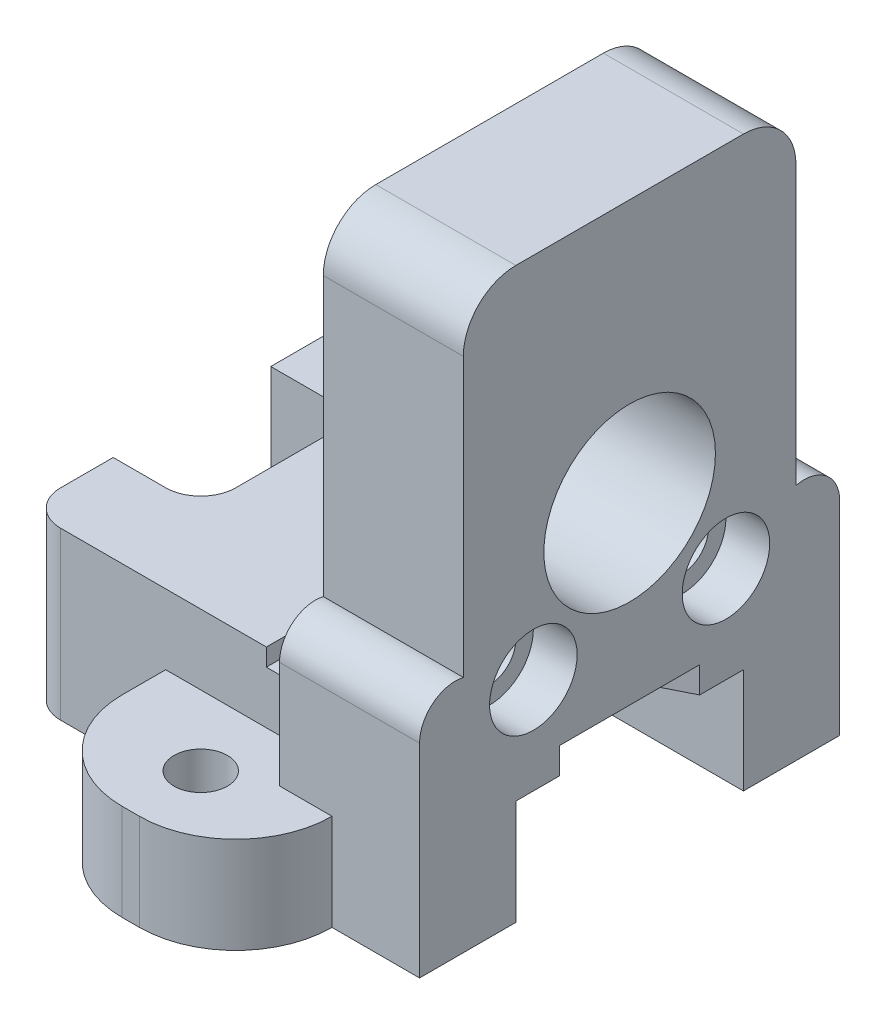
SolidWorks part; units mm, degrees
ref_plane "Front Plane" through (0, 0, 0) normal (0, 0, 1) x (1, 0, 0)
ref_plane "Top Plane" through (0, 0, 0) normal (0, 1, 0) x (1, 0, 0)
ref_plane "Right Plane" through (0, 0, 0) normal (1, 0, 0) x (0, 0, -1)
sketch "Sketch1" plane through (0, 0, 0) normal (0, 1, 0) x (1, 0, 0)
  line L0 (-1, -3) -> (23, -3)
  line L1 (0, 0) -> (22, 0)
  line L2 (0, 0) -> (0, 13)
  line L3 (0, 13) -> (22, 13)
  line L4 (22, 0) -> (22, 13)
  line L5 (25, -1) -> (25, 14)
  line L6 (-1, 16) -> (23, 16)
  line L7 (-3, -1) -> (-3, 14)
  line L8 (-3, -3) -> (25, -3) construction
  line L9 (25, -3) -> (25, 16) construction
  line L10 (-3, 16) -> (25, 16) construction
  line L11 (-3, -3) -> (-3, 16) construction
  line L12 (23, -3) -> (25, -3)
  line L13 (25, -3) -> (25, -1)
  line L14 (25, 16) -> (23, 16)
  line L15 (25, 16) -> (25, 14)
  arc A2 (-1, 16) -> (-3, 14) centre (-1, 14) ccw
  arc A3 (-1, -3) -> (-3, -1) centre (-1, -1) cw
  dimension "D1" = 22
  dimension "D2" = 13
  dimension "D3" = 3
extrude "Boss-Extrude1" add sketch "Sketch1" along normal blind 6
sketch "Sketch2" plane through (0, 6, 0) normal (0, 1, 0) x (1, 0, 0)
  line L0 (25, 14) -> (25, -1)
  line L1 (23, -3) -> (-1, -3)
  line L2 (-3, -1) -> (-3, 14)
  line L3 (-1, 16) -> (23, 16)
  line L4 (25, 16) -> (-1, 16) construction
  line L5 (23, -3) -> (25, -3)
  line L6 (25, -3) -> (25, -1)
  line L7 (25, 14) -> (25, 16)
  line L8 (25, 16) -> (23, 16)
  arc A1 (-1, -3) -> (-3, -1) centre (-1, -1) cw
  arc A2 (-3, 14) -> (-1, 16) centre (-1, 14) cw
extrude "Boss-Extrude2" add sketch "Sketch2" along normal blind 3.5
sketch "Sketch3" plane through (0, 0, 0) normal (0, -1, 0) x (1, 0, 0)
  line L0 (-1, 3) -> (25, 3) construction
  line L1 (5, 3) -> (17, 3)
  line L2 (5, 3) -> (5, 5.5)
  line L3 (10.5, 11) -> (11.5, 11)
  line L4 (17, 3) -> (17, 5.5)
  line L5 (25, -16) -> (-1, -16) construction
  line L6 (17, -16) -> (5, -16)
  line L7 (17, -16) -> (17, -18.5)
  line L8 (11.5, -24) -> (10.5, -24)
  line L9 (5, -16) -> (5, -18.5)
  line L10 (25, 3) -> (25, -16) construction
  line L11 (-3, -14) -> (-3, 1) construction
  arc A0 (17, -18.5) -> (11.5, -24) centre (11.5, -18.5) cw
  arc A1 (10.5, -24) -> (5, -18.5) centre (10.5, -18.5) cw
  arc A2 (5, 5.5) -> (10.5, 11) centre (10.5, 5.5) cw
  arc A3 (11.5, 11) -> (17, 5.5) centre (11.5, 5.5) cw
  point P16 (17, -17.25)
  point P19 (17, -24)
  point P26 (17, 11)
  dimension "D7" = 5.5
  dimension "D1" = 8
  dimension "D2" = 8
  dimension "D3" = 8
  dimension "D4" = 8
  dimension "D5" = 8
  dimension "D6" = 8
extrude "Boss-Extrude3" add sketch "Sketch3" against normal up to surface (9.5 mm away) up to face at (6.8619, 9.5, -6.5)
sketch "Sketch4" plane through (0, 0, 0) normal (0, -1, 0) x (-1, 0, 0)
  line L0 (-17, 18.5) -> (-17, 16) construction
  line L2 (-10.5, 24) -> (-11.5, 24) construction
  line L3 (-11.5, -11) -> (-10.5, -11) construction
  line L4 (-5, -5.5) -> (-5, -3) construction
  circle A0 centre (-11, 20) radius 1.525
  circle A1 centre (-11, -7) radius 1.524
  point P9 (-11, 24)
  dimension "D1" = 3.048
  dimension "D2" = 3.05
  dimension "D3" = 6
  dimension "D4" = 4
  dimension "D5" = 4
  dimension "D6" = 6
extrude "Cut-Extrude1" cut sketch "Sketch4" against normal through all
sketch "Sketch5" plane through (25, 0, 0) normal (1, 0, 0) x (0, 0, -1)
  line L0 (-3, 0) -> (16, 0) construction
  line L1 (11, 0) -> (2, 0)
  line L2 (11, 0) -> (11, 5.5)
  line L3 (11, 5.5) -> (2, 5.5)
  line L4 (2, 0) -> (2, 5.5)
  line L5 (-3, 9.5) -> (-3, 0) construction
  line L6 (16, 9.5) -> (16, 0) construction
  line L7 (-3, 9.5) -> (16, 9.5) construction
  dimension "D1" = 5
  dimension "D2" = 5
  dimension "D3" = 4
extrude "Cut-Extrude2" cut sketch "Sketch5" against normal through all
fillet "Fillet1" radius 2 4 edges at (-1.5, 5.5, -2) (-1.5, 5.5, -11) (23.5, 5.5, -11) (23.5, 5.5, -2)
sketch "Sketch6" plane through (0, 9.5, 0) normal (0, 1, 0) x (1, 0, 0)
  line L0 (-1, -3) -> (5, -3) construction
  line L1 (17, 16) -> (5, 16)
  line L2 (17, 16) -> (17, 29.009)
  line L3 (17, 29.009) -> (5, 29.009)
  line L4 (5, 16) -> (5, 29.009)
  line L5 (19.0682, -16.009) -> (3.2299, -16.009)
  line L6 (19.0682, -16.009) -> (19.0682, -3)
  line L7 (19.0682, -3) -> (3.2299, -3)
  line L8 (3.2299, -16.009) -> (3.2299, -3)
extrude "Cut-Extrude3" cut sketch "Sketch6" against normal blind 4
sketch "Sketch7" plane through (0, 9.5, 0) normal (0, 1, 0) x (1, 0, 0)
  line L0 (-1, -3) -> (25, -3) construction
  line L1 (23, 16) -> (22, 16)
  line L2 (25, 14) -> (25, -1)
  line L3 (23, -3) -> (22, -3)
  line L4 (22, 16) -> (22, -3)
  line L5 (25, 16) -> (-1, 16) construction
  line L6 (25, -3) -> (25, 16) construction
  line L7 (23, -3) -> (25, -3)
  line L8 (25, -3) -> (25, -1)
  line L9 (25, 14) -> (25, 16)
  line L10 (25, 16) -> (23, 16)
  point P12 (25, 16)
  dimension "D1" = 3
extrude "Boss-Extrude4" add sketch "Sketch7" along normal blind 23
sketch "Sketch8" plane through (0, 9.5, 0) normal (0, 1, 0) x (1, 0, 0)
  line L0 (-3, 14) -> (-3, -1) construction
  line L1 (-3, 2) -> (0, 2)
  line L2 (-3, 2) -> (-3, 11)
  line L3 (-3, 11) -> (0, 11)
  line L4 (2, 4) -> (2, 9)
  line L5 (22, 16) -> (-1, 16) construction
  line L6 (-1, -3) -> (22, -3) construction
  arc A0 (0, 2) -> (2, 4) centre (0, 4) ccw
  arc A1 (0, 11) -> (2, 9) centre (0, 9) cw
  point P12 (2, 2)
  dimension "D4" = 2
  dimension "D1" = 5
  dimension "D2" = 5
  dimension "D3" = 5
extrude "Cut-Extrude4" cut sketch "Sketch8" against normal blind 23
sketch "Sketch9" plane through (22, 0, 0) normal (-1, 0, 0) x (0, 0, 1)
  line L2 (-16, 32.5) -> (3, 32.5) construction
  line L4 (-16, 9.5) -> (3, 9.5) construction
  circle A0 centre (-6.5, 17.5) radius 4.9
  point P10 (-6.5, 32.5)
  dimension "D1" = 9.8
  dimension "D2" = 8
extrude "Cut-Extrude6" cut sketch "Sketch9" against normal blind 23 contours A0
sketch "Sketch10" plane through (22, 0, 0) normal (-1, 0, 0) x (0, 0, 1)
  line L0 (-16, 32.5) -> (-16, 9.5) construction
  line L1 (-16, 9.5) -> (3, 9.5) construction
  line L2 (3, 32.5) -> (3, 9.5) construction
  line L3 (3, 32.5) -> (-16, 32.5) construction
  line L4 (0.5, 7.2165) -> (-13.5, 7.2165) construction
  line L5 (0.5, 7.2165) -> (0.5, 29.2165) construction
  line L6 (0.5, 29.2165) -> (-13.5, 29.2165) construction
  line L7 (-13.5, 7.2165) -> (-13.5, 29.2165) construction
  circle A0 centre (-12, 11.5) radius 1.5
  circle A1 centre (-1, 11.5) radius 1.5
  point P14 (-6.5, 29.2165)
  point P17 (-6.5, 32.5)
  dimension "D5" = 3
  dimension "D6" = 3
  dimension "D1" = 4
  dimension "D2" = 2
  dimension "D3" = 4
  dimension "D4" = 2
  dimension "D7" = 14
  dimension "D8" = 22
extrude "Cut-Extrude7" cut sketch "Sketch10" against normal blind 23
sketch "Sketch11" plane through (25, 0, 0) normal (1, 0, 0) x (0, 0, -1)
  line L0 (-5.5, 5.5) -> (-5.5, 0) construction
  line L1 (-3, 0) -> (-5.5, 0)
  line L2 (-3, 0) -> (-3, 13.6179)
  line L3 (-3, 13.6179) -> (-3.5, 13.6179)
  line L4 (-5.5, 0) -> (-5.5, 11.6179)
  line L5 (18.5, 5.5) -> (18.5, 0) construction
  line L6 (16, 0) -> (18.5, 0)
  line L7 (16, 0) -> (16, 13.6179)
  line L8 (16, 13.6179) -> (16.5, 13.6179)
  line L9 (18.5, 0) -> (18.5, 11.6179)
  arc A0 (-3.5, 13.6179) -> (-5.5, 11.6179) centre (-3.5, 11.6179) ccw
  arc A1 (16.5, 13.6179) -> (18.5, 11.6179) centre (16.5, 11.6179) cw
  dimension "D1" = 2
  dimension "D2" = 2
extrude "Boss-Extrude5" add sketch "Sketch11" against normal up to surface (3 mm away) up to face at (22, 11.5, 0.5)
fillet "Fillet2" radius 2.5 1 edges at (22, 4.75, 3)
fillet "Fillet3" radius 2.5 1 edges at (22, 4.75, -16)
sketch "Sketch12" plane through (0, 6, 0) normal (0, -1, 0) x (1, 0, 0)
  line L0 (22, 0) -> (22, -13) construction
  line L1 (22, -8) -> (2, -8)
  line L2 (22, -8) -> (22, -5)
  line L3 (22, -5) -> (2, -5)
  line L4 (2, -8) -> (2, -5)
  line L5 (2, -9) -> (2, -4) construction
  point P8 (2, -6.5)
  dimension "D1" = 3
extrude "Cut-Extrude8" cut sketch "Sketch12" against normal blind 1.5
sketch "Sketch13" plane through (0, 9.5, 0) normal (0, 1, 0) x (1, 0, 0)
  line L0 (-1, -3) -> (19.5, -3) construction
  line L1 (19.5, 16) -> (2, 16)
  line L2 (19.5, 16) -> (19.5, -3)
  line L3 (19.5, -3) -> (2, -3)
  line L4 (2, 16) -> (2, -3)
  line L5 (2, 4) -> (2, 9) construction
sketch "Sketch14" plane through (22, 0, 0) normal (-1, 0, 0) x (0, 0, 1)
  line L0 (-18.5, 9.5) -> (5.5, 9.5) construction
  line L1 (-16, 32.5) -> (3, 32.5)
  line L2 (-16, 32.5) -> (-16, 13.6179)
  line L3 (-16, 9.5) -> (3, 9.5)
  line L4 (3, 32.5) -> (3, 13.6179)
  line L5 (3, 32.5) -> (3, 13.6179) construction
  line L6 (-16, 9.5) -> (-18.5, 9.5)
  line L7 (-18.5, 9.5) -> (-18.5, 11.6179)
  line L8 (3, 9.5) -> (5.5, 9.5)
  line L9 (5.5, 9.5) -> (5.5, 11.6179)
  arc A0 (-18.5, 11.6179) -> (-16, 13.6179) centre (-16.45, 11.6179) cw
  arc A1 (5.5, 11.6179) -> (3, 13.6179) centre (3.45, 11.6179) ccw
extrude "Boss-Extrude6" add sketch "Sketch14" along normal blind 8
sketch "Sketch15" plane through (22, 0, 0) normal (1, 0, 0) x (0, 0, -1)
  circle A0 centre (6.5, 17.5) radius 4.9
  circle A1 centre (6.5, 17.5) radius 4.9 construction
  circle A2 centre (1, 11.5) radius 1.5
  circle A3 centre (1, 11.5) radius 1.5 construction
  circle A4 centre (12, 11.5) radius 1.5
  circle A5 centre (12, 11.5) radius 1.5 construction
extrude "Cut-Extrude9" cut sketch "Sketch15" against normal through all
sketch "Sketch16" plane through (25, 0, 0) normal (1, 0, 0) x (0, 0, -1)
  line L1 (-10.4282, 36.3162) -> (19.1331, 36.3162)
  line L2 (-10.4282, 36.3162) -> (-10.4282, -4.4665)
  line L3 (-10.4282, -4.4665) -> (19.1331, -4.4665)
  line L4 (19.1331, 36.3162) -> (19.1331, -4.4665)
extrude "Cut-Extrude10" cut sketch "Sketch16" against normal blind 3
sketch "Sketch17" plane through (0, 0, 0) normal (0, -1, 0) x (1, 0, 0)
  line L0 (22, -13) -> (0, -13) construction
  line L1 (22, -18.5) -> (14, -18.5)
  line L2 (22, -18.5) -> (22, -13)
  line L3 (22, -13) -> (14, -13)
  line L4 (14, -18.5) -> (14, -13)
  line L5 (14, -16) -> (14, 3) construction
  line L7 (22, 0) -> (14, 0)
  line L8 (22, 0) -> (22, 5.5)
  line L9 (22, 5.5) -> (14, 5.5)
  line L10 (14, 0) -> (14, 5.5)
  point P14 (0, 0)
extrude "Boss-Extrude7" add sketch "Sketch17" against normal up to surface (9.5 mm away) up to face at (17.5044, 9.5, -17.1206)
sketch "Sketch18" plane through (0, 6, 0) normal (0, -1, 0) x (-1, 0, 0)
  line L0 (-22, 2.5) -> (-17, 5)
  line L1 (-22, 0) -> (-22, 5) construction
  line L2 (-22, 5) -> (-2, 5) construction
  line L3 (-17, 5) -> (-17, 8)
  line L4 (-2, 8) -> (-22, 8) construction
  line L5 (-17, 8) -> (-22, 10.5)
  line L6 (-22, 8) -> (-22, 13) construction
  line L7 (-22, 10.5) -> (-22, 2.5)
  line L8 (-22, 5) -> (-2, 5) construction
  dimension "D1" = 2.5
  dimension "D2" = 5
extrude "Cut-Extrude11" cut sketch "Sketch18" against normal up to surface (1.5 mm away) up to face at (12, 7.5, -6.5)
sketch "Sketch19" plane through (0, 9.5, 0) normal (0, 1, 0) x (1, 0, 0)
  line L0 (19.5, 16) -> (2, 16) construction
  line L1 (14, -3) -> (10.75, -3)
  line L2 (14, -3) -> (14, 16)
  line L3 (14, 16) -> (10.75, 16)
  line L4 (10.75, -3) -> (10.75, 16)
sketch "Sketch20" plane through (22, 0, 0) normal (1, 0, 0) x (0, 0, -1)
  circle A0 centre (1, 11.5) radius 2.5
  circle A1 centre (12, 11.5) radius 2.5
  circle A2 centre (1, 11.5) radius 1.5 construction
  point P5 (0, 0)
  dimension "D1" = 5
  dimension "D2" = 5
extrude "Cut-Extrude12" cut sketch "Sketch20" against normal blind 2.5
extrude "Cut-Extrude13" cut sketch "Sketch19" against normal blind 1
chamfer "Chamfer1" distance 1 angle 45 1 edges at (14, 17.5, -11.4)
fillet "Fillet4" radius 3 2 edges at (18, 32.5, -16) (18, 32.5, 3)
